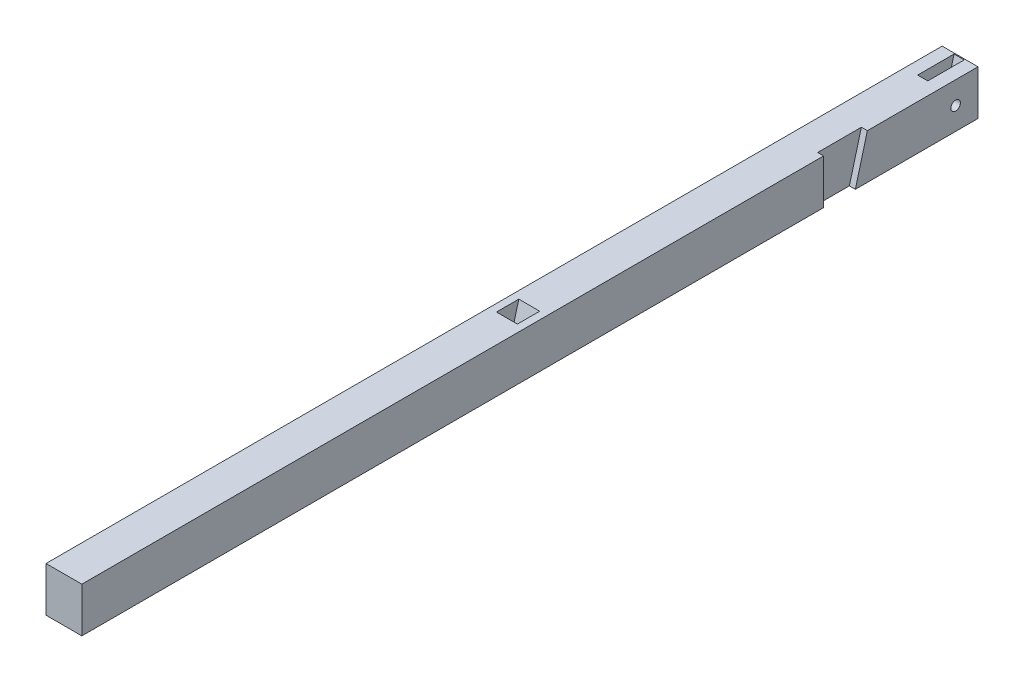
SolidWorks part; units mm, degrees
ref_plane "Front Plane" through (0, 0, 0) normal (0, 0, 1) x (1, 0, 0)
ref_plane "Top Plane" through (0, 0, 0) normal (0, 1, 0) x (1, 0, 0)
ref_plane "Right Plane" through (0, 0, 0) normal (1, 0, 0) x (0, 0, -1)
sketch "Sketch1" plane through (0, 0, 0) normal (1, 0, 0) x (0, 0, -1)
  line L0 (0, -10.7728) -> (0, 31.5488) construction
  line L1 (-3.5, 0) -> (0, 0) construction
  line L2 (0, 0) -> (3.5, 0) construction
  line L3 (3.5, 0) -> (150, 0)
  line L4 (150, 0) -> (150, 15)
  line L5 (150, 15) -> (5.7792, 15)
  line L6 (5.7792, 15) -> (2.4339, 2.5152)
  line L7 (-1.7, 3.0594) -> (-1.7, 15)
  line L8 (5.7792, 15) -> (0, 15) construction
  line L9 (-1.7, 15) -> (-150, 15)
  line L10 (-150, 15) -> (-150, 0)
  line L11 (-150, 0) -> (-3.5, 0)
  line L12 (0, 15) -> (-1.7, 15) construction
  line L13 (2.4339, 2.5152) -> (1.6421, -0.44) construction
  line L14 (1.6421, -0.44) -> (0, 0) construction
  arc A0 (-3.5, 0) -> (-1.7, 3.0594) centre (0, 0) cw
  arc A1 (2.4339, 2.5152) -> (3.5, 0) centre (0, 0) cw
  dimension "D1" = 1.7
  dimension "D2" = 150
  dimension "D3" = 300
  dimension "D4" = 7
  dimension "D5" = 15
  dimension "D6" = 15
extrude "Boss-Extrude1" add sketch "Sketch1" along normal mid plane 7
sketch "Sketch2" plane through (-3.5, 0, 0) normal (-1, 0, 0) x (0, 0, 1)
  line L1 (-150, 0) -> (150, 0)
  line L2 (-150, 0) -> (-150, 15)
  line L3 (-150, 15) -> (150, 15)
  line L4 (150, 0) -> (150, 15)
extrude "Boss-Extrude2" add sketch "Sketch2" along normal blind 2.5
sketch "Sketch3" plane through (3.5, 0, 0) normal (1, 0, 0) x (0, 0, -1)
  line L1 (-150, 0) -> (150, 0)
  line L2 (-150, 0) -> (-150, 15)
  line L3 (-150, 15) -> (150, 15)
  line L4 (150, 0) -> (150, 15)
extrude "Boss-Extrude3" add sketch "Sketch3" along normal blind 0.5
sketch "Sketch4" plane through (4, 0, 0) normal (1, 0, 0) x (0, 0, -1)
  line L0 (98.3, 0) -> (98.3, 15)
  line L1 (-150, 0) -> (150, 0)
  line L2 (-150, 0) -> (-150, 15)
  line L3 (-150, 15) -> (150, 15)
  line L4 (150, 0) -> (150, 15)
  line L5 (108.9396, 0) -> (112.9589, 15)
  line L6 (100, -26.7949) -> (100, 31.143) construction
  line L7 (0, -10.7728) -> (0, 31.5488) construction
  line L8 (0, 0) -> (100, -26.7949) construction
  line L9 (100, -26.7949) -> (113.1221, 22.1774) construction
  line L10 (109.3072, 7.94) -> (110.9493, 7.5) construction
  line L11 (98.3, 0) -> (100, 0) construction
  line L12 (142.5, 15) -> (142.5, 7.5) construction
  line L13 (142.5, 7.5) -> (142.5, 0) construction
  line L14 (142.5, 7.5) -> (150, 7.5) construction
  point P22 (110.9493, 7.5)
  point P26 (142.5, 7.5)
  line M15 (-150, 15) -> (-150, 0)
  line M16 (-150, 0) -> (150, 0)
  line M17 (150, 0) -> (150, 15)
  line M18 (150, 15) -> (-150, 15)
  dimension "D1" = 100
  dimension "D2" = 1.7
  dimension "D3" = 15
extrude "Boss-Extrude4" add sketch "Sketch4" along normal blind 2 contours L0 M16 M18 M15 | L5 L1 M17 M18 region at (4, 7.5, 25.85) region at (4, 7.3713, -130.4574)
hole_wizard "M3 Clearance Hole1" positions "3DSketch1" profile "Sketch5" hole size "M3" standard "ANSI Metric" end condition through all
sketch3d "3DSketch1"
  point P0 (4, 7.5, -142.5)
sketch "Sketch5" plane through (4, 7.5, -142.5) normal (0, 1, 0) x (0, 0, -1)
  line L0 (0, 0) -> (0, 10)
  line L1 (0, 10) -> (1.6, 10)
  line L2 (1.6, 10) -> (1.6, 0)
  line L5 (1.6, 0) -> (0, 0)
  line L11 (0, -6.35) -> (0, 107.95) construction
  dimension "Thru Hole Dia." = 3.2
  dimension "Thru Hole Depth" = 10
hole_wizard "M3 Clearance Hole2" positions "3DSketch2" profile "Sketch6" hole size "M3" standard "ANSI Metric" end condition through all
sketch3d "3DSketch2"
  point P0 (4, 7.5, -142.5)
sketch "Sketch6" plane through (4, 7.5, -142.5) normal (0, 1, 0) x (0, 0, 1)
  line L0 (0, 0) -> (0, 2)
  line L1 (0, 2) -> (1.6, 2)
  line L2 (1.6, 2) -> (1.6, 0)
  line L5 (1.6, 0) -> (0, 0)
  line L11 (0, -6.35) -> (0, 107.95) construction
  dimension "Thru Hole Dia." = 3.2
  dimension "Thru Hole Depth" = 2
sketch "Sketch7" plane through (0, 0, 0) normal (1, 0, 0) x (0, 0, -1)
  line L0 (137.5, 7.5) -> (137.5, 15)
  line L1 (150, 15) -> (5.7792, 15) construction
  line L2 (147.3296, 6.2059) -> (149.686, 15)
  line L4 (137.5, 15) -> (149.686, 15)
  arc A0 (147.3296, 6.2059) -> (137.5, 7.5) centre (142.5, 7.5) cw
  dimension "D1" = 5
  dimension "D2" = 15
extrude "Cut-Extrude2" cut sketch "Sketch7" against normal mid plane 3.4
